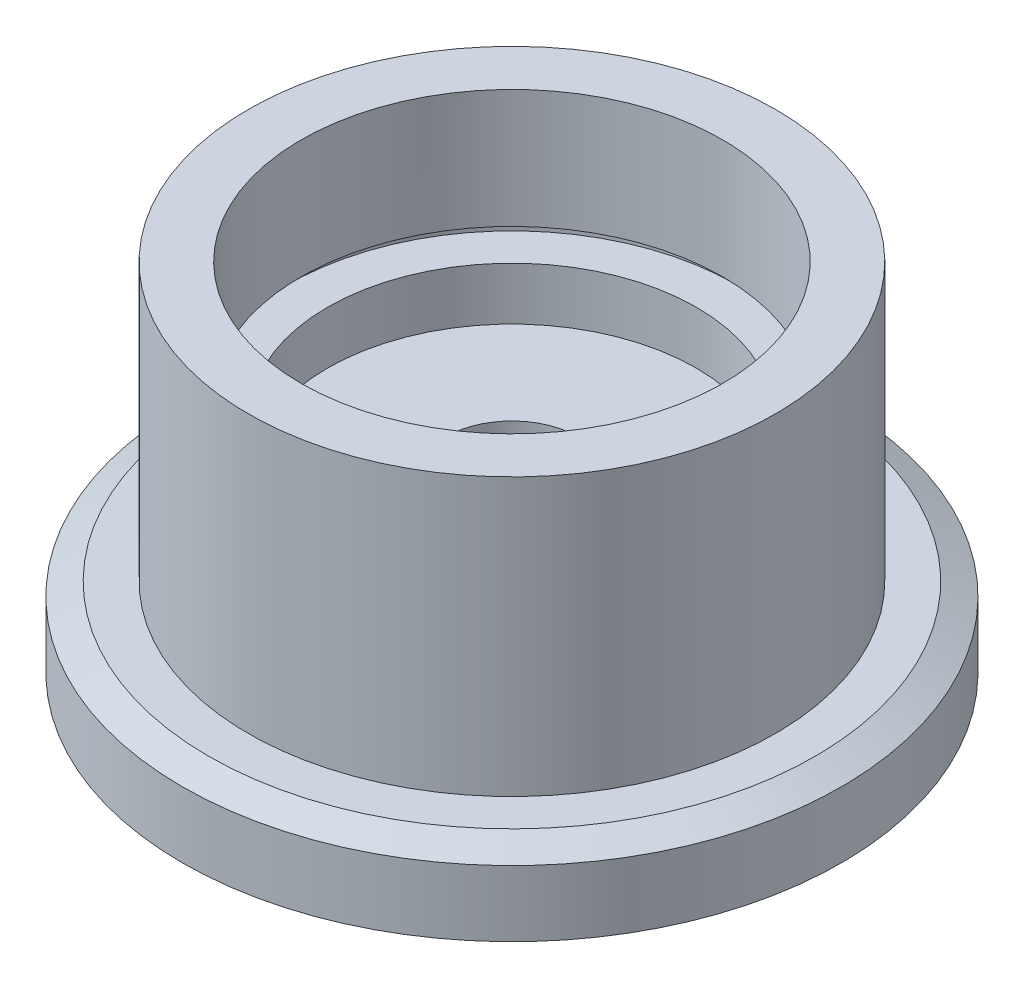
SolidWorks part; units mm, degrees
ref_plane "Plan de face" through (0, 0, 0) normal (0, 0, 1) x (1, 0, 0)
ref_plane "Plan de dessus" through (0, 0, 0) normal (0, 1, 0) x (1, 0, 0)
ref_plane "Plan de droite" through (0, 0, 0) normal (1, 0, 0) x (0, 0, -1)
sketch "Esquisse1" plane through (0, 0, 0) normal (0, 1, 0) x (1, 0, 0)
  circle A0 centre (0, 0) radius 12.5
  dimension "D1" = 25
extrude "Boss.-Extru.1" add sketch "Esquisse1" along normal blind 3.5
sketch "Esquisse2" plane through (0, 3.5, 0) normal (0, 1, 0) x (1, 0, 0)
  circle A0 centre (0, 0) radius 10
  dimension "D1" = 20
extrude "Boss.-Extru.2" add sketch "Esquisse2" along normal blind 10.5
sketch "Esquisse3" plane through (0, 0, 0) normal (0, -1, 0) x (1, 0, 0)
  circle A0 centre (0, 0) radius 2.5
  dimension "D1" = 5
extrude "Enlèv. mat.-Extru.1" cut sketch "Esquisse3" against normal blind 7
sketch "Esquisse4" plane through (0, 7, 0) normal (0, -1, 0) x (1, 0, 0)
  circle A0 centre (0, 0) radius 7
  dimension "D1" = 14
extrude "Enlèv. mat.-Extru.2" cut sketch "Esquisse4" against normal blind 2
sketch "Esquisse5" plane through (0, 9, 0) normal (0, -1, 0) x (1, 0, 0)
  circle A0 centre (0, 0) radius 8.5
  dimension "D1" = 17
extrude "Enlèv. mat.-Extru.3" cut sketch "Esquisse5" against normal blind 0.5
sketch "Esquisse6" plane through (0, 14, 0) normal (0, 1, 0) x (1, 0, 0)
  circle A0 centre (0, 0) radius 8
  dimension "D1" = 16
extrude "Enlèv. mat.-Extru.4" cut sketch "Esquisse6" against normal blind 5
chamfer "Chanfrein1" distance 0.5 distance2 1 1 edges at (0, 3.5, 12.5) first distance on face at (0, 3.5, 12.5)
chamfer "Chanfrein2" distance 1 distance2 0.5 1 edges at (0, 0, 12.5) first distance on face at (0, 0, -2.5)
